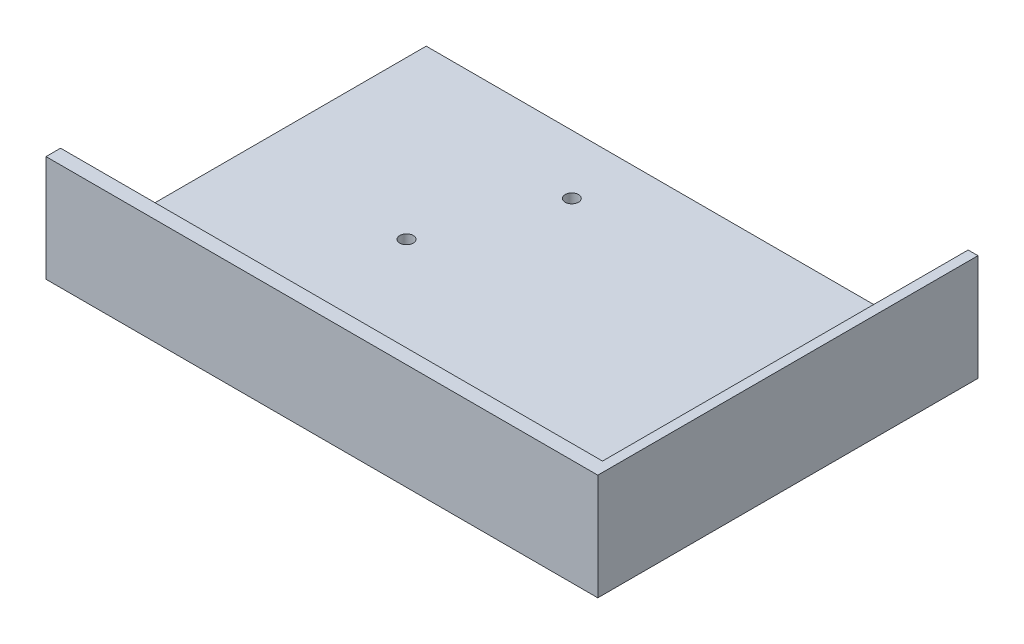
SolidWorks part; units mm, degrees
ref_plane "Front Plane" through (0, 0, 0) normal (0, 0, 1) x (1, 0, 0)
ref_plane "Top Plane" through (0, 0, 0) normal (0, 1, 0) x (1, 0, 0)
ref_plane "Right Plane" through (0, 0, 0) normal (1, 0, 0) x (0, 0, -1)
sketch "Sketch1" plane through (0, 0, 0) normal (0, 1, 0) x (1, 0, 0)
  line L1 (-140.2, -96.6) -> (140.2, -96.6)
  line L2 (-140.2, -96.6) -> (-140.2, 96.6)
  line L3 (-140.2, 96.6) -> (140.2, 96.6)
  line L4 (140.2, -96.6) -> (140.2, 96.6)
  line L5 (-140.2, -96.6) -> (140.2, 96.6) construction
  line L6 (-140.2, 96.6) -> (140.2, -96.6) construction
  dimension "D1" = 280.4
  dimension "D2" = 193.2
extrude "Shell Block" add sketch "Sketch1" along normal blind 27
ref_plane "Shell Front" through (0, 27, 0) normal (0, 1, 0) x (1, 0, 0)
sketch "Sketch2" plane through (0, 27, 0) normal (0, 1, 0) x (1, 0, 0)
  line L1 (-137.7, -92.9) -> (137.7, -92.9)
  line L2 (-137.7, -92.9) -> (-137.7, 92.9)
  line L3 (-137.7, 92.9) -> (137.7, 92.9)
  line L4 (137.7, -92.9) -> (137.7, 92.9)
  line L5 (-137.7, -92.9) -> (137.7, 92.9) construction
  line L6 (-137.7, 92.9) -> (137.7, -92.9) construction
  dimension "D1" = 275.4
  dimension "D2" = 185.8
extrude "Front Opening" cut sketch "Sketch2" against normal blind 1.5
ref_plane "Under Lip" through (0, 25.5, 0) normal (0, 1, 0) x (1, 0, 0)
sketch "Sketch3" plane through (0, 25.5, 0) normal (0, 1, 0) x (1, 0, 0)
  line L1 (-137.7, -94.1) -> (137.7, -94.1)
  line L2 (-137.7, -94.1) -> (-137.7, 94.1)
  line L3 (-137.7, 94.1) -> (137.7, 94.1)
  line L4 (137.7, -94.1) -> (137.7, 94.1)
  line L5 (-137.7, -94.1) -> (137.7, 94.1) construction
  line L6 (-137.7, 94.1) -> (137.7, -94.1) construction
  dimension "D1" = 275.4
  dimension "D2" = 188.2
extrude "Display Pocket" cut sketch "Sketch3" against normal blind 22.5
ref_plane "Back Inner" through (0, 3, 0) normal (0, 1, 0) x (1, 0, 0)
sketch "Sketch4" plane through (0, 3, 0) normal (0, 1, 0) x (1, 0, 0)
  line L1 (-69, 28) -> (-66, 28)
  line L2 (-69, 28) -> (-69, 84)
  line L3 (-69, 84) -> (-66, 84)
  line L4 (-66, 28) -> (-66, 84)
  line L6 (-69, -84) -> (-66, -84)
  line L7 (-69, -84) -> (-69, -28)
  line L8 (-69, -28) -> (-66, -28)
  line L9 (-66, -84) -> (-66, -28)
  line L11 (-77, 28) -> (-74, 28)
  line L12 (-77, 28) -> (-77, 84)
  line L13 (-77, 84) -> (-74, 84)
  line L14 (-74, 28) -> (-74, 84)
  line L16 (-77, -84) -> (-74, -84)
  line L17 (-77, -84) -> (-77, -28)
  line L18 (-77, -28) -> (-74, -28)
  line L19 (-74, -84) -> (-74, -28)
  line L21 (-85, 28) -> (-82, 28)
  line L22 (-85, 28) -> (-85, 84)
  line L23 (-85, 84) -> (-82, 84)
  line L24 (-82, 28) -> (-82, 84)
  line L26 (-85, -84) -> (-82, -84)
  line L27 (-85, -84) -> (-85, -28)
  line L28 (-85, -28) -> (-82, -28)
  line L29 (-82, -84) -> (-82, -28)
  line L31 (-93, 28) -> (-90, 28)
  line L32 (-93, 28) -> (-93, 84)
  line L33 (-93, 84) -> (-90, 84)
  line L34 (-90, 28) -> (-90, 84)
  line L36 (-93, -84) -> (-90, -84)
  line L37 (-93, -84) -> (-93, -28)
  line L38 (-93, -28) -> (-90, -28)
  line L39 (-90, -84) -> (-90, -28)
  line L41 (-101, 28) -> (-98, 28)
  line L42 (-101, 28) -> (-101, 84)
  line L43 (-101, 84) -> (-98, 84)
  line L44 (-98, 28) -> (-98, 84)
  line L46 (-101, -84) -> (-98, -84)
  line L47 (-101, -84) -> (-101, -28)
  line L48 (-101, -28) -> (-98, -28)
  line L49 (-98, -84) -> (-98, -28)
  line L51 (-109, 28) -> (-106, 28)
  line L52 (-109, 28) -> (-109, 84)
  line L53 (-109, 84) -> (-106, 84)
  line L54 (-106, 28) -> (-106, 84)
  line L56 (-109, -84) -> (-106, -84)
  line L57 (-109, -84) -> (-109, -28)
  line L58 (-109, -28) -> (-106, -28)
  line L59 (-106, -84) -> (-106, -28)
  line L61 (-117, 28) -> (-114, 28)
  line L62 (-117, 28) -> (-117, 84)
  line L63 (-117, 84) -> (-114, 84)
  line L64 (-114, 28) -> (-114, 84)
  line L66 (-117, -84) -> (-114, -84)
  line L67 (-117, -84) -> (-117, -28)
  line L68 (-117, -28) -> (-114, -28)
  line L69 (-114, -84) -> (-114, -28)
  line L71 (-125, 28) -> (-122, 28)
  line L72 (-125, 28) -> (-125, 84)
  line L73 (-125, 84) -> (-122, 84)
  line L74 (-122, 28) -> (-122, 84)
  line L76 (-125, -84) -> (-122, -84)
  line L77 (-125, -84) -> (-125, -28)
  line L78 (-125, -28) -> (-122, -28)
  line L79 (-122, -84) -> (-122, -28)
extrude "Vent Slots" cut sketch "Sketch4" against normal blind 4
sketch "Sketch5" plane through (0, 0, 0) normal (1, 0, 0) x (0, 0, -1)
  line L1 (-35, 5) -> (35, 5)
  line L2 (-35, 5) -> (-35, 21)
  line L3 (-35, 21) -> (35, 21)
  line L4 (35, 5) -> (35, 21)
extrude "Cable Exit (-X short side)" cut sketch "Sketch5" against normal blind 141.2
sketch "Sketch6" plane through (0, 3, 0) normal (0, 1, 0) x (1, 0, 0)
  circle A0 centre (-40, -45) radius 1.7
  circle A1 centre (-40, 45) radius 1.7
  circle A2 centre (40, -45) radius 1.7
  circle A3 centre (40, 45) radius 1.7
  circle A4 centre (-52, -15) radius 1.7
  circle A5 centre (-52, 15) radius 1.7
  circle A6 centre (52, -15) radius 1.7
  circle A7 centre (52, 15) radius 1.7
  circle A8 centre (-12, -82) radius 1.7
  circle A9 centre (-12, 82) radius 1.7
  circle A10 centre (12, -82) radius 1.7
  circle A11 centre (12, 82) radius 1.7
  circle A12 centre (-124, -12) radius 1.7
  circle A13 centre (-124, 12) radius 1.7
  circle A14 centre (124, -12) radius 1.7
  circle A15 centre (124, 12) radius 1.7
extrude "Bolt Holes" cut sketch "Sketch6" against normal blind 4
sketch "Sketch7" plane through (0, 0, 0) normal (0, 1, 0) x (1, 0, 0)
  line L1 (-200, -200) -> (0, -200)
  line L2 (-200, -200) -> (-200, 200)
  line L3 (-200, 200) -> (0, 200)
  line L4 (0, -200) -> (0, 200)
extrude "Keep one half (X)" cut sketch "Sketch7" against normal through all and the other way through all
sketch "Sketch8" plane through (0, 0, 0) normal (0, 1, 0) x (1, 0, 0)
  line L1 (-200, 0) -> (200, 0)
  line L2 (-200, 0) -> (-200, 200)
  line L3 (-200, 200) -> (200, 200)
  line L4 (200, 0) -> (200, 200)
extrude "Keep one quarter (Z)" cut sketch "Sketch8" against normal through all and the other way through all
equation "\"DispL\"= 274.2"
equation "\"DispW\"= 187.0"
equation "\"DispT\"= 20.0"
equation "\"Clr\"= 0.6"
equation "\"Wall\"= 2.5"
equation "\"BackT\"= 3.0"
equation "\"CableRoom\"= 4.0"
equation "\"LipW\"= 1.2"
equation "\"LipT\"= 1.5"
equation "\"CableW\"= 70.0"
equation "\"CableH\"= 16.0"
equation "\"BoltD\"= 3.4"
equation "\"ShellL\"= \"DispL\" + 2 * \"Clr\" + 2 * \"Wall\""
equation "\"ShellW\"= \"DispW\" + 2 * \"Clr\" + 2 * \"Wall\""
equation "\"ShellH\"= \"BackT\" + \"DispT\" + \"CableRoom\""
equation "\"D1@Sketch1\" = \"ShellL\""
equation "\"D2@Sketch1\" = \"ShellW\""
equation "\"D1@Shell Block\" = \"ShellH\""
equation "\"D1@Shell Front\" = \"ShellH\""
equation "\"D1@Sketch2\" = \"DispL\" + 2 * \"Clr\""
equation "\"D2@Sketch2\" = \"DispW\" + 2 * \"Clr\" - 2 * \"LipW\""
equation "\"D1@Front Opening\" = \"LipT\""
equation "\"D1@Under Lip\" = \"ShellH\" - \"LipT\""
equation "\"D1@Sketch3\" = \"DispL\" + 2 * \"Clr\""
equation "\"D2@Sketch3\" = \"DispW\" + 2 * \"Clr\""
equation "\"D1@Display Pocket\" = \"ShellH\" - \"LipT\" - \"BackT\""
equation "\"D1@Back Inner\" = \"BackT\""
